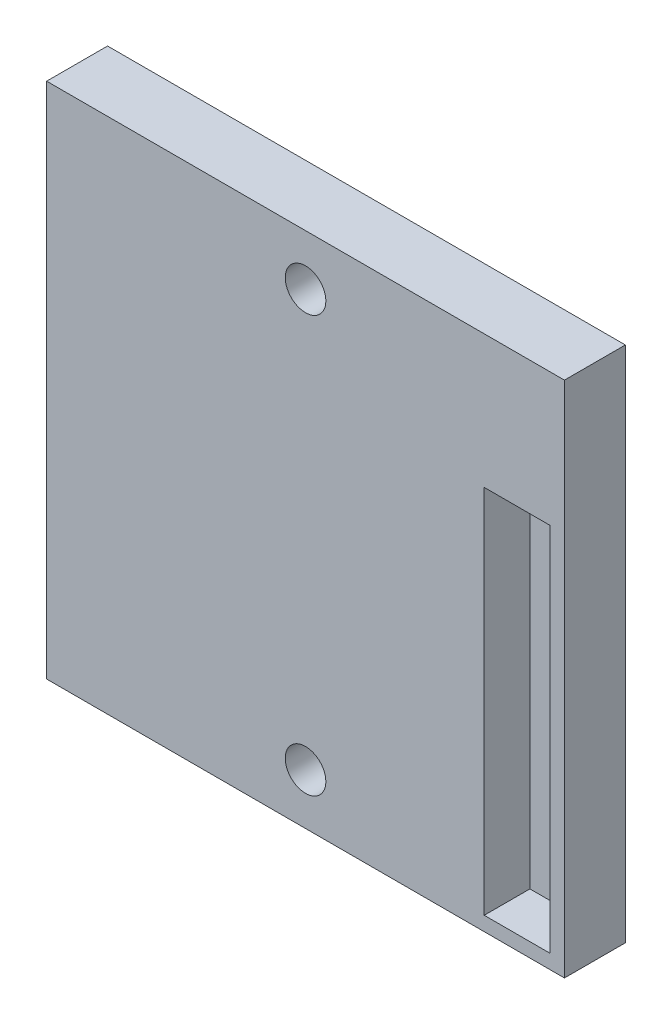
SolidWorks part; units mm, degrees
material "ABS"
ref_plane "Plano frontal" through (0, 0, 0) normal (0, 0, 1) x (1, 0, 0)
ref_plane "Plano superior" through (0, 0, 0) normal (0, 1, 0) x (1, 0, 0)
ref_plane "Plano direito" through (0, 0, 0) normal (1, 0, 0) x (0, 0, -1)
sketch "Esboço1" plane through (0, 0, 0) normal (0, 0, 1) x (1, 0, 0)
  line L1 (25.5, 25.5) -> (-25.5, 25.5)
  line L2 (25.5, 25.5) -> (25.5, -25.5)
  line L3 (25.5, -25.5) -> (-25.5, -25.5)
  line L4 (-25.5, 25.5) -> (-25.5, -25.5)
  line L5 (25.5, 25.5) -> (-25.5, -25.5) construction
  line L6 (25.5, -25.5) -> (-25.5, 25.5) construction
  point P0 (0, 0)
  dimension "D1" = 51
  dimension "D2" = 51
extrude "Ressalto-extrusão1" add sketch "Esboço1" along normal blind 6
sketch "Esboço2" plane through (0, 0, 0) normal (0, 0, -1) x (-1, 0, 0)
  line L0 (25.5, -25.5) -> (-25.5, -25.5) construction
  line L1 (-24.1, 12.4) -> (-17.6, 12.4)
  line L2 (-24.1, 12.4) -> (-24.1, -24.1)
  line L3 (-24.1, -24.1) -> (-17.6, -24.1)
  line L4 (-17.6, 12.4) -> (-17.6, -24.1)
  line L5 (-25.5, -25.5) -> (-25.5, 25.5) construction
  dimension "D1" = 6.5
  dimension "D2" = 36.5
  dimension "D3" = 1.4
  dimension "D4" = 1.4
extrude "Corte-extrusão1" cut sketch "Esboço2" against normal blind 4.5
sketch "Esboço3" plane through (0, 0, 6) normal (0, 0, 1) x (1, 0, 0)
  line L0 (25.5, 25.5) -> (-25.5, 25.5) construction
  line L1 (-25.5, -25.5) -> (25.5, -25.5) construction
  circle A0 centre (0, -20.5) radius 2
  circle A1 centre (0, 20.5) radius 2
  dimension "D1" = 4
  dimension "D2" = 5
  dimension "D3" = 5
extrude "Corte-extrusão2" cut sketch "Esboço3" against normal through all
ref_plane "Plano1" through (0, 0, -10) normal (0, 0, 1) x (1, 0, 0)
mirror "Espelhar2" about plane through (0, 0, -10) normal (0, 0, 1) of bodies 104
delete or keep bodies "Corpo-Excluir/Manter 1" type delete bodies bodies 104
